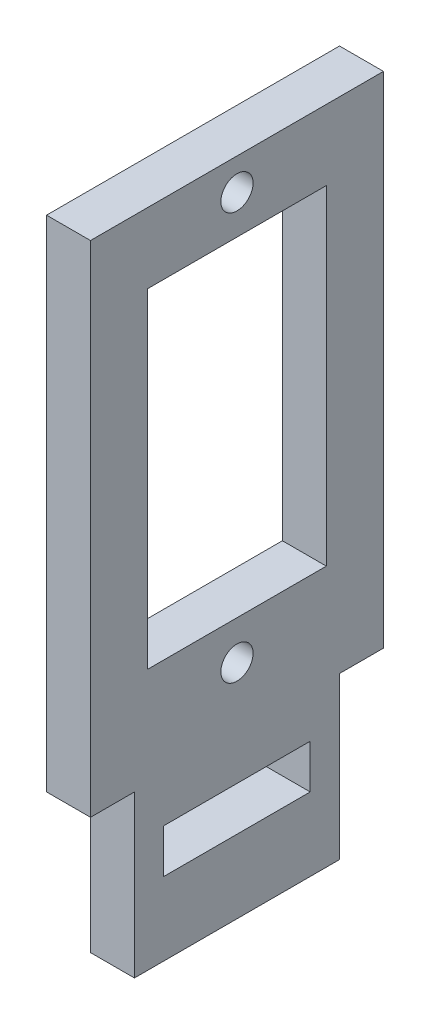
SolidWorks part; units mm, degrees
ref_plane "Front Plane" through (0, 0, 0) normal (0, 0, 1) x (1, 0, 0)
ref_plane "Top Plane" through (0, 0, 0) normal (0, 1, 0) x (1, 0, 0)
ref_plane "Right Plane" through (0, 0, 0) normal (1, 0, 0) x (0, 0, -1)
sketch "Sketch1" plane through (0, 0, 0) normal (1, 0, 0) x (0, 0, -1)
  line L0 (0, 8) -> (20, 8) construction
  line L1 (0, 0) -> (20, 0)
  line L2 (0, 0) -> (0, 45.1)
  line L3 (0, 45.1) -> (20, 45.1)
  line L4 (20, 0) -> (20, 45.1)
  line L5 (5, 8) -> (15, 8)
  line L6 (5, 5) -> (15, 5)
  line L7 (5, 5) -> (5, 8)
  line L9 (15, 5) -> (15, 8)
  point P7 (10, 8)
  dimension "D1" = 10
  dimension "D2" = 45.1
  dimension "D3" = 20
  dimension "D4" = 8
  dimension "D5" = 3
  dimension "D6" = 5
extrude "Boss-Extrude1" add sketch "Sketch1" along normal blind 3
sketch "Sketch2" plane through (0, 0, 0) normal (-1, 0, 0) x (0, 0, 1)
  line L0 (-10, 45.1) -> (-10, 42.95) construction
  line L1 (-20, 45.1) -> (0, 45.1) construction
  line L2 (-10, 42.95) -> (-10, 15.15) construction
  line L4 (-16.1, 17.8) -> (-3.9, 17.8)
  line L5 (-16.1, 17.8) -> (-16.1, 40.3)
  line L6 (-16.1, 40.3) -> (-3.9, 40.3)
  line L7 (-3.9, 17.8) -> (-3.9, 40.3)
  line L8 (-16.1, 17.8) -> (-3.9, 40.3) construction
  line L9 (-16.1, 40.3) -> (-3.9, 17.8) construction
  line L10 (-20, 0) -> (-17, 0)
  line L11 (-20, 0) -> (-20, 11)
  line L12 (-20, 11) -> (-17, 11)
  line L13 (-17, 0) -> (-17, 11)
  line L14 (0, 0) -> (-3, 0)
  line L15 (0, 0) -> (0, 11)
  line L16 (0, 11) -> (-3, 11)
  line L17 (-3, 0) -> (-3, 11)
  circle A0 centre (-10, 42.95) radius 1.1
  circle A1 centre (-10, 15.15) radius 1.1
  point P7 (-10, 29.05)
  dimension "D1" = 2.15
  dimension "D2" = 2.2
  dimension "D4" = 2.2
  dimension "D3" = 27.8
  dimension "D5" = 22.5
  dimension "D6" = 12.2
  dimension "D7" = 3
  dimension "D8" = 3
  dimension "D9" = 11
  dimension "D10" = 11
extrude "Cut-Extrude1" cut sketch "Sketch2" against normal blind 3
